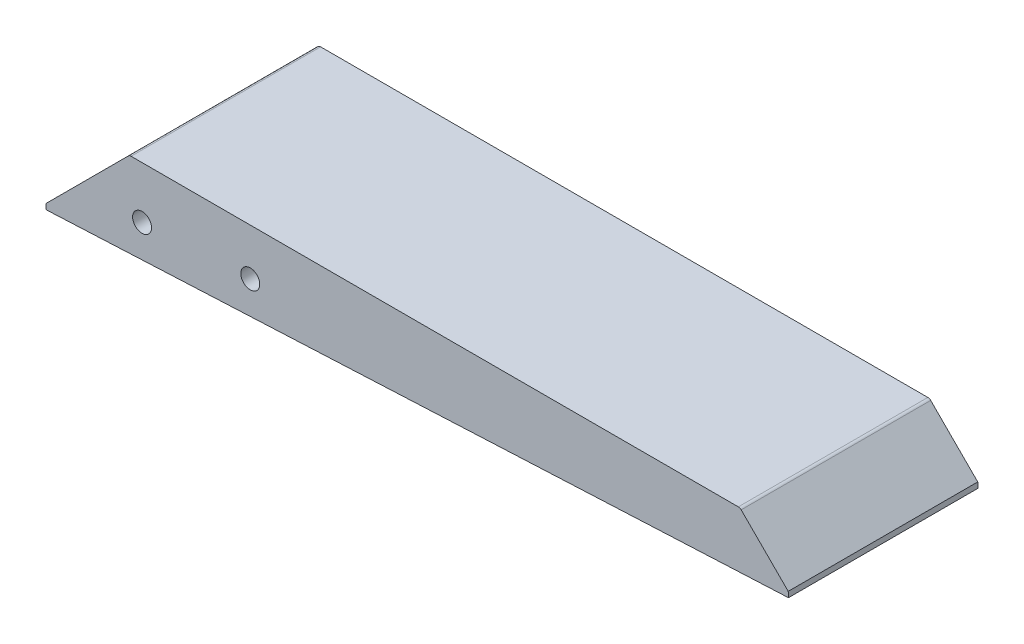
SolidWorks part; units mm, degrees
ref_plane "前视基准面" through (0, 0, 0) normal (0, 0, 1) x (1, 0, 0)
ref_plane "上视基准面" through (0, 0, 0) normal (0, 1, 0) x (1, 0, 0)
ref_plane "右视基准面" through (0, 0, 0) normal (1, 0, 0) x (0, 0, -1)
other "Configuration Table"
sketch "草图1" plane through (0, 0, 0) normal (0, 0, 1) x (1, 0, 0)
  line L0 (166.8324, 7.5944) -> (168.9537, 9.7157) construction
  line L1 (168.9537, 9.7157) -> (160.2639, 18.4056) construction
  line L2 (158.1425, 16.2843) -> (166.8324, 7.5944) construction
  line L3 (157.6217, 19.5) -> (45.4745, 19.5) construction
  line L4 (45.4745, 16.5) -> (157.6217, 16.5) construction
  line L5 (29.7639, 1.0944) -> (44.9537, 16.2843) construction
  line L6 (42.8324, 18.4056) -> (27.6425, 3.2157) construction
  line L7 (27.6425, 3.2157) -> (29.7639, 1.0944) construction
  line L8 (166.8324, 7.5944) -> (168.9537, 9.7157)
  line L9 (168.9537, 9.7157) -> (160.2639, 18.4056)
  line L10 (158.1425, 16.2843) -> (166.8324, 7.5944)
  line L11 (157.6217, 19.5) -> (45.4745, 19.5)
  line L12 (45.4745, 16.5) -> (157.6217, 16.5)
  line L13 (29.7639, 1.0944) -> (44.9537, 16.2843)
  line L14 (42.8324, 18.4056) -> (27.6425, 3.2157)
  line L15 (27.6425, 3.2157) -> (29.7639, 1.0944)
  line L16 (29.7639, 1.0944) -> (166.8324, 7.5944)
  arc A0 (158.1425, 16.2843) -> (157.6217, 16.5) centre (157.6217, 15.7634) ccw construction
  arc A1 (160.2639, 18.4056) -> (157.6217, 19.5) centre (157.6217, 15.7634) ccw construction
  arc A2 (45.4745, 16.5) -> (44.9537, 16.2843) centre (45.4745, 15.7634) ccw construction
  arc A3 (45.4745, 19.5) -> (42.8324, 18.4056) centre (45.4745, 15.7634) ccw construction
  arc A4 (158.1425, 16.2843) -> (157.6217, 16.5) centre (157.6217, 15.7634) ccw
  arc A5 (160.2639, 18.4056) -> (157.6217, 19.5) centre (157.6217, 15.7634) ccw
  arc A6 (45.4745, 16.5) -> (44.9537, 16.2843) centre (45.4745, 15.7634) ccw
  arc A7 (45.4745, 19.5) -> (42.8324, 18.4056) centre (45.4745, 15.7634) ccw
extrude "凸台-拉伸1" add sketch "草图1" against normal blind 35 contours L12 A6 L13 L16 L10 A4 region at (94.8139, 10.1061, 0)
sketch "草图2" plane through (0.015, -0.3163, 0) normal (0.0474, -0.9989, 0) x (0.9989, 0.0474, 0)
  line L0 (165.5048, -1.5) -> (31.2823, -1.5)
  line L1 (31.2823, -1.5) -> (31.2823, -33.5)
  line L2 (31.2823, -33.5) -> (165.5048, -33.5)
  line L3 (165.5048, -33.5) -> (165.5048, -1.5)
  line L4 (167.0048, 0) -> (29.7823, 0)
  line L5 (29.7823, 0) -> (29.7823, -35)
  line L6 (29.7823, -35) -> (167.0048, -35)
  line L7 (167.0048, -35) -> (167.0048, 0)
  line L8 (167.0048, 0) -> (29.7823, 0)
  line L9 (29.7823, 0) -> (29.7823, -35)
  line L10 (29.7823, -35) -> (167.0048, -35)
  line L11 (167.0048, -35) -> (167.0048, 0)
  dimension "D1" = 0
  dimension "D2" = 1.5
extrude "凸台-拉伸2" add sketch "草图2" along normal blind 1
fillet "圆角1" radius 2 4 edges at (31.2859, 0.666, -33.5) (165.3577, 7.0239, -33.5) (165.3577, 7.0239, -1.5) (31.2859, 0.666, -1.5)
sketch "草图3" plane through (0, 0, 0) normal (0, 0, 1) x (1, 0, 0)
  line L0 (166.8797, 6.5955) -> (29.8112, 0.0955) construction
  line L1 (29.8112, 0.0955) -> (29.7639, 1.0944) construction
  circle A0 centre (47.5068, 6.9414) radius 1.75
  circle A1 centre (67.4842, 7.8923) radius 1.75
  dimension "D1" = 3.5
  dimension "D3" = 20
  dimension "D4" = 6
  dimension "D5" = 18
  dimension "D2" = 2
extrude "切除-拉伸1" cut sketch "草图3" against normal blind 6.2
sketch "草图4" plane through (0, 0, -35) normal (0, 0, -1) x (-1, 0, 0)
  circle A0 centre (-47.5068, 6.9414) radius 1.75 construction
  circle A1 centre (-67.4842, 7.8923) radius 1.75 construction
  circle A2 centre (-47.5068, 6.9414) radius 1.75
  circle A3 centre (-67.4842, 7.8923) radius 1.75
extrude "切除-拉伸2" cut sketch "草图4" against normal blind 6.55
sketch "草图6" plane through (0.015, -0.3163, 0) normal (0.0474, -0.9989, 0) x (0.9989, 0.0474, 0)
  line L1199 (144.5332, -18.3417) -> (144.2984, -18.2008)
  line L1200 (144.2984, -18.2008) -> (143.9227, -18.2947)
  line L1201 (143.9227, -18.2947) -> (142.7956, -19.4688)
  line L1202 (142.7956, -19.4688) -> (142.279, -19.8915)
  line L1203 (142.279, -19.8915) -> (142.1381, -19.8915)
  line L1204 (142.1381, -19.8915) -> (142.0911, -19.7506)
  line L1205 (142.0911, -19.7506) -> (142.6547, -18.2478)
  line L1206 (142.6547, -18.2478) -> (142.7016, -17.8251)
  line L1207 (142.7016, -17.8251) -> (142.4668, -17.4963)
  line L1208 (142.4668, -17.4963) -> (141.9972, -17.4494)
  line L1209 (141.9972, -17.4494) -> (141.6684, -17.7312)
  line L1210 (141.6684, -17.7312) -> (141.2457, -18.3887)
  line L1211 (141.2457, -18.3887) -> (140.2595, -19.3749)
  line L1212 (140.2595, -19.3749) -> (139.2263, -20.1263)
  line L1213 (139.2263, -20.1263) -> (138.8036, -20.3142)
  line L1214 (138.8036, -20.3142) -> (138.6157, -20.3142)
  line L1215 (138.6157, -20.3142) -> (138.5218, -20.2203)
  line L1216 (138.5218, -20.2203) -> (138.5218, -19.9854)
  line L1217 (138.5218, -19.9854) -> (138.6627, -19.6097)
  line L1218 (138.6627, -19.6097) -> (139.4611, -18.4356)
  line L1219 (139.4611, -18.4356) -> (139.4611, -18.1069)
  line L1220 (139.4611, -18.1069) -> (139.2732, -17.872)
  line L1221 (139.2732, -17.872) -> (139.0384, -17.7781)
  line L1222 (139.0384, -17.7781) -> (138.6627, -17.872)
  line L1223 (138.6627, -17.872) -> (138.0052, -18.6235)
  line L1224 (138.0052, -18.6235) -> (137.5825, -19.3279)
  line L1225 (137.5825, -19.3279) -> (137.3477, -20.1263)
  line L1226 (137.3477, -20.1263) -> (137.3477, -20.4081)
  line L1227 (137.3477, -20.4081) -> (137.4886, -20.7838)
  line L1228 (137.4886, -20.7838) -> (137.9113, -21.1595)
  line L1229 (137.9113, -21.1595) -> (138.1931, -21.2535)
  line L1230 (138.1931, -21.2535) -> (138.7566, -21.2535)
  line L1231 (138.7566, -21.2535) -> (139.6959, -20.8778)
  line L1232 (139.6959, -20.8778) -> (140.6352, -20.1733)
  line L1233 (140.6352, -20.1733) -> (140.7761, -20.2203)
  line L1234 (140.7761, -20.2203) -> (140.6352, -20.8308)
  line L1235 (140.6352, -20.8308) -> (140.5413, -20.9247)
  line L1236 (140.5413, -20.9247) -> (138.5218, -21.817)
  line L1237 (138.5218, -21.817) -> (137.9582, -22.1928)
  line L1238 (137.9582, -22.1928) -> (137.6295, -22.5215)
  line L1239 (137.6295, -22.5215) -> (137.4416, -22.8503)
  line L1240 (137.4416, -22.8503) -> (137.4416, -23.2729)
  line L1241 (137.4416, -23.2729) -> (137.6765, -23.6487)
  line L1242 (137.6765, -23.6487) -> (138.0052, -23.8835)
  line L1243 (138.0052, -23.8835) -> (138.3809, -24.0244)
  line L1244 (138.3809, -24.0244) -> (139.1793, -24.0713)
  line L1245 (139.1793, -24.0713) -> (139.8368, -23.8835)
  line L1246 (139.8368, -23.8835) -> (140.4473, -23.5078)
  line L1247 (140.4473, -23.5078) -> (141.0109, -22.8503)
  line L1248 (141.0109, -22.8503) -> (141.4806, -21.817)
  line L1249 (141.4806, -21.817) -> (141.6215, -21.3004)
  line L1250 (141.6215, -21.3004) -> (142.8425, -20.596)
  line L1251 (142.8425, -20.596) -> (143.7348, -19.8445)
  line L1252 (143.7348, -19.8445) -> (144.4863, -18.9522)
  line L1253 (144.4863, -18.9522) -> (144.5802, -18.7644)
  line L1254 (144.5802, -18.7644) -> (144.5332, -18.3417)
  line L1255 (140.2125, -21.9579) -> (140.2125, -22.0988)
  line L1256 (140.2125, -22.0988) -> (140.0247, -22.4745)
  line L1257 (140.0247, -22.4745) -> (139.555, -22.9912)
  line L1258 (139.555, -22.9912) -> (139.0854, -23.226)
  line L1259 (139.0854, -23.226) -> (138.6627, -23.226)
  line L1260 (138.6627, -23.226) -> (138.5218, -23.0851)
  line L1261 (138.5218, -23.0851) -> (138.5688, -22.8503)
  line L1262 (138.5688, -22.8503) -> (138.8036, -22.5685)
  line L1263 (138.8036, -22.5685) -> (140.0716, -21.911)
  line L1264 (140.0716, -21.911) -> (140.2125, -21.9579)
  line L1265 (156.9788, -14.8663) -> (156.744, -14.7254)
  line L1266 (156.744, -14.7254) -> (156.4152, -14.7254)
  line L1267 (156.4152, -14.7254) -> (156.1334, -14.9133)
  line L1268 (156.1334, -14.9133) -> (156.0395, -15.1481)
  line L1269 (156.0395, -15.1481) -> (155.9925, -16.0874)
  line L1270 (155.9925, -16.0874) -> (155.5698, -17.1676)
  line L1271 (155.5698, -17.1676) -> (154.7715, -18.3417)
  line L1272 (154.7715, -18.3417) -> (153.9731, -19.0462)
  line L1273 (153.9731, -19.0462) -> (153.6913, -18.9992)
  line L1274 (153.6913, -18.9992) -> (153.6913, -18.3417)
  line L1275 (153.6913, -18.3417) -> (153.8791, -17.7312)
  line L1276 (153.8791, -17.7312) -> (153.8791, -17.3085)
  line L1277 (153.8791, -17.3085) -> (153.6913, -17.0736)
  line L1278 (153.6913, -17.0736) -> (153.5034, -16.9797)
  line L1279 (153.5034, -16.9797) -> (153.2686, -16.9797)
  line L1280 (153.2686, -16.9797) -> (153.0338, -17.0736)
  line L1281 (153.0338, -17.0736) -> (152.8459, -17.2615)
  line L1282 (152.8459, -17.2615) -> (152.3763, -18.1069)
  line L1283 (152.3763, -18.1069) -> (151.39, -19.1401)
  line L1284 (151.39, -19.1401) -> (151.1082, -19.3279)
  line L1285 (151.1082, -19.3279) -> (150.9204, -19.281)
  line L1286 (150.9204, -19.281) -> (150.9673, -18.9053)
  line L1287 (150.9673, -18.9053) -> (151.2022, -18.2478)
  line L1288 (151.2022, -18.2478) -> (152.0006, -16.7919)
  line L1289 (152.0006, -16.7919) -> (151.9536, -16.3692)
  line L1290 (151.9536, -16.3692) -> (151.5779, -16.1344)
  line L1291 (151.5779, -16.1344) -> (151.2022, -16.2283)
  line L1292 (151.2022, -16.2283) -> (150.9204, -16.5101)
  line L1293 (150.9204, -16.5101) -> (150.122, -17.872)
  line L1294 (150.122, -17.872) -> (149.8872, -18.6235)
  line L1295 (149.8872, -18.6235) -> (149.0418, -19.4219)
  line L1296 (149.0418, -19.4219) -> (148.4782, -19.8445)
  line L1297 (148.4782, -19.8445) -> (148.2434, -19.9385)
  line L1298 (148.2434, -19.9385) -> (147.9616, -19.9385)
  line L1299 (147.9616, -19.9385) -> (147.7268, -19.7976)
  line L1300 (147.7268, -19.7976) -> (147.3511, -19.4219)
  line L1301 (147.3511, -19.4219) -> (147.3511, -19.281)
  line L1302 (147.3511, -19.281) -> (149.1827, -17.5433)
  line L1303 (149.1827, -17.5433) -> (149.2766, -17.3554)
  line L1304 (149.2766, -17.3554) -> (149.2766, -17.1206)
  line L1305 (149.2766, -17.1206) -> (149.0418, -16.8388)
  line L1306 (149.0418, -16.8388) -> (148.6661, -16.7919)
  line L1307 (148.6661, -16.7919) -> (148.3373, -16.9328)
  line L1308 (148.3373, -16.9328) -> (146.6466, -18.4826)
  line L1309 (146.6466, -18.4826) -> (146.5057, -18.4826)
  line L1310 (146.5057, -18.4826) -> (145.6604, -17.5433)
  line L1311 (145.6604, -17.5433) -> (145.1907, -17.4963)
  line L1312 (145.1907, -17.4963) -> (145.0029, -17.5903)
  line L1313 (145.0029, -17.5903) -> (144.815, -17.8251)
  line L1314 (144.815, -17.8251) -> (144.815, -18.1069)
  line L1315 (144.815, -18.1069) -> (145.7543, -19.281)
  line L1316 (145.7543, -19.281) -> (145.7543, -19.3749)
  line L1317 (145.7543, -19.3749) -> (144.1106, -21.2065)
  line L1318 (144.1106, -21.2065) -> (143.9227, -21.5822)
  line L1319 (143.9227, -21.5822) -> (143.9697, -21.864)
  line L1320 (143.9697, -21.864) -> (144.2515, -22.0988)
  line L1321 (144.2515, -22.0988) -> (144.5802, -22.0988)
  line L1322 (144.5802, -22.0988) -> (144.815, -22.0049)
  line L1323 (144.815, -22.0049) -> (146.4588, -20.2203)
  line L1324 (146.4588, -20.2203) -> (146.5997, -20.2203)
  line L1325 (146.5997, -20.2203) -> (147.0693, -20.6429)
  line L1326 (147.0693, -20.6429) -> (147.492, -20.8778)
  line L1327 (147.492, -20.8778) -> (148.2904, -20.9247)
  line L1328 (148.2904, -20.9247) -> (149.0888, -20.549)
  line L1329 (149.0888, -20.549) -> (149.7463, -19.9385)
  line L1330 (149.7463, -19.9385) -> (149.8872, -19.9385)
  line L1331 (149.8872, -19.9385) -> (150.169, -20.2672)
  line L1332 (150.169, -20.2672) -> (150.4038, -20.4081)
  line L1333 (150.4038, -20.4081) -> (150.9204, -20.4551)
  line L1334 (150.9204, -20.4551) -> (151.2491, -20.3611)
  line L1335 (151.2491, -20.3611) -> (151.8127, -20.0324)
  line L1336 (151.8127, -20.0324) -> (152.5172, -19.3749)
  line L1337 (152.5172, -19.3749) -> (152.6581, -19.4219)
  line L1338 (152.6581, -19.4219) -> (152.752, -19.6567)
  line L1339 (152.752, -19.6567) -> (153.0338, -19.9385)
  line L1340 (153.0338, -19.9385) -> (153.4565, -20.1263)
  line L1341 (153.4565, -20.1263) -> (154.067, -20.0794)
  line L1342 (154.067, -20.0794) -> (154.5366, -19.8915)
  line L1343 (154.5366, -19.8915) -> (155.2881, -19.3279)
  line L1344 (155.2881, -19.3279) -> (155.7577, -18.8583)
  line L1345 (155.7577, -18.8583) -> (156.2743, -18.1538)
  line L1346 (156.2743, -18.1538) -> (156.744, -17.3085)
  line L1347 (156.744, -17.3085) -> (157.1197, -16.0404)
  line L1348 (157.1197, -16.0404) -> (157.1197, -15.1951)
  line L1349 (157.1197, -15.1951) -> (156.9788, -14.8663)
  line L1599 (103.178, -10.8157) -> (102.5205, -10.4869)
  line L1600 (102.5205, -10.4869) -> (101.7221, -10.2521)
  line L1601 (101.7221, -10.2521) -> (100.2192, -10.2521)
  line L1602 (100.2192, -10.2521) -> (99.5148, -10.5339)
  line L1603 (99.5148, -10.5339) -> (99.0921, -10.8626)
  line L1604 (99.0921, -10.8626) -> (97.4014, -11.6141)
  line L1605 (97.4014, -11.6141) -> (95.8985, -12.1307)
  line L1606 (95.8985, -12.1307) -> (94.8653, -12.2716)
  line L1607 (94.8653, -12.2716) -> (94.6305, -12.4594)
  line L1608 (94.6305, -12.4594) -> (94.5365, -12.6473)
  line L1609 (94.5365, -12.6473) -> (94.5835, -12.9291)
  line L1610 (94.5835, -12.9291) -> (95.0531, -13.3987)
  line L1611 (95.0531, -13.3987) -> (95.4289, -13.5866)
  line L1612 (95.4289, -13.5866) -> (96.0864, -13.7744)
  line L1613 (96.0864, -13.7744) -> (97.6362, -13.7744)
  line L1614 (97.6362, -13.7744) -> (97.824, -14.1032)
  line L1615 (97.824, -14.1032) -> (97.871, -14.9955)
  line L1616 (97.871, -14.9955) -> (97.7771, -15.3242)
  line L1617 (97.7771, -15.3242) -> (96.556, -15.7939)
  line L1618 (96.556, -15.7939) -> (95.8046, -16.2635)
  line L1619 (95.8046, -16.2635) -> (94.9592, -15.9817)
  line L1620 (94.9592, -15.9817) -> (94.4896, -15.9817)
  line L1621 (94.4896, -15.9817) -> (94.1608, -16.1226)
  line L1622 (94.1608, -16.1226) -> (94.0199, -16.2635)
  line L1623 (94.0199, -16.2635) -> (93.926, -16.5453)
  line L1624 (93.926, -16.5453) -> (94.2078, -17.4846)
  line L1625 (94.2078, -17.4846) -> (94.2548, -18.8935)
  line L1626 (94.2548, -18.8935) -> (94.3956, -19.7389)
  line L1627 (94.3956, -19.7389) -> (94.6305, -20.3964)
  line L1628 (94.6305, -20.3964) -> (94.9123, -20.866)
  line L1629 (94.9123, -20.866) -> (95.4758, -21.4296)
  line L1630 (95.4758, -21.4296) -> (95.9924, -21.6644)
  line L1631 (95.9924, -21.6644) -> (96.603, -21.7114)
  line L1632 (96.603, -21.7114) -> (97.3544, -21.4766)
  line L1633 (97.3544, -21.4766) -> (97.5423, -21.4766)
  line L1634 (97.5423, -21.4766) -> (97.5892, -21.6644)
  line L1635 (97.5892, -21.6644) -> (97.4483, -22.3219)
  line L1636 (97.4483, -22.3219) -> (97.2605, -22.7916)
  line L1637 (97.2605, -22.7916) -> (96.7908, -23.3551)
  line L1638 (96.7908, -23.3551) -> (95.1471, -23.8248)
  line L1639 (95.1471, -23.8248) -> (93.6442, -24.1066)
  line L1640 (93.6442, -24.1066) -> (92.7519, -24.1535)
  line L1641 (92.7519, -24.1535) -> (92.4701, -24.2944)
  line L1642 (92.4701, -24.2944) -> (92.1883, -24.6232)
  line L1643 (92.1883, -24.6232) -> (92.0944, -25.0928)
  line L1644 (92.0944, -25.0928) -> (92.3292, -25.6564)
  line L1645 (92.3292, -25.6564) -> (92.7519, -26.0791)
  line L1646 (92.7519, -26.0791) -> (93.4094, -26.4548)
  line L1647 (93.4094, -26.4548) -> (93.973, -26.6426)
  line L1648 (93.973, -26.6426) -> (95.5228, -26.6426)
  line L1649 (95.5228, -26.6426) -> (96.4621, -26.4078)
  line L1650 (96.4621, -26.4078) -> (100.5949, -24.905)
  line L1651 (100.5949, -24.905) -> (102.9431, -24.2005)
  line L1652 (102.9431, -24.2005) -> (103.3658, -24.2475)
  line L1653 (103.3658, -24.2475) -> (103.9764, -25.2807)
  line L1654 (103.9764, -25.2807) -> (104.446, -25.7034)
  line L1655 (104.446, -25.7034) -> (104.9156, -25.9382)
  line L1656 (104.9156, -25.9382) -> (105.3853, -26.0321)
  line L1657 (105.3853, -26.0321) -> (105.9019, -25.9851)
  line L1658 (105.9019, -25.9851) -> (106.4185, -25.7503)
  line L1659 (106.4185, -25.7503) -> (106.7942, -25.3746)
  line L1660 (106.7942, -25.3746) -> (107.029, -24.7641)
  line L1661 (107.029, -24.7641) -> (107.029, -24.2005)
  line L1662 (107.029, -24.2005) -> (106.8881, -23.6839)
  line L1663 (106.8881, -23.6839) -> (106.5594, -23.1203)
  line L1664 (106.5594, -23.1203) -> (105.8549, -22.3689)
  line L1665 (105.8549, -22.3689) -> (104.9156, -21.7114)
  line L1666 (104.9156, -21.7114) -> (103.8824, -21.2417)
  line L1667 (103.8824, -21.2417) -> (103.178, -21.0539)
  line L1668 (103.178, -21.0539) -> (102.6144, -21.1009)
  line L1669 (102.6144, -21.1009) -> (102.4265, -21.1948)
  line L1670 (102.4265, -21.1948) -> (102.2387, -21.4766)
  line L1671 (102.2387, -21.4766) -> (102.3326, -21.8523)
  line L1672 (102.3326, -21.8523) -> (102.6144, -22.181)
  line L1673 (102.6144, -22.181) -> (102.5205, -22.3689)
  line L1674 (102.5205, -22.3689) -> (101.2524, -22.5567)
  line L1675 (101.2524, -22.5567) -> (100.2662, -22.7916)
  line L1676 (100.2662, -22.7916) -> (99.9374, -22.7446)
  line L1677 (99.9374, -22.7446) -> (99.9374, -22.6037)
  line L1678 (99.9374, -22.6037) -> (100.2662, -21.9462)
  line L1679 (100.2662, -21.9462) -> (100.5949, -20.7721)
  line L1680 (100.5949, -20.7721) -> (100.7358, -20.6782)
  line L1681 (100.7358, -20.6782) -> (101.5342, -20.4903)
  line L1682 (101.5342, -20.4903) -> (102.8492, -20.3494)
  line L1683 (102.8492, -20.3494) -> (103.5067, -20.1146)
  line L1684 (103.5067, -20.1146) -> (103.8355, -19.7859)
  line L1685 (103.8355, -19.7859) -> (103.9764, -19.4571)
  line L1686 (103.9764, -19.4571) -> (104.5399, -18.6587)
  line L1687 (104.5399, -18.6587) -> (105.3383, -17.015)
  line L1688 (105.3383, -17.015) -> (105.3383, -16.3575)
  line L1689 (105.3383, -16.3575) -> (105.2444, -16.0757)
  line L1690 (105.2444, -16.0757) -> (105.0096, -15.7)
  line L1691 (105.0096, -15.7) -> (104.1642, -14.9955)
  line L1692 (104.1642, -14.9955) -> (103.6006, -14.7137)
  line L1693 (103.6006, -14.7137) -> (102.5674, -14.4319)
  line L1694 (102.5674, -14.4319) -> (101.5812, -14.4319)
  line L1695 (101.5812, -14.4319) -> (101.2524, -14.5259)
  line L1696 (101.2524, -14.5259) -> (100.8298, -14.4789)
  line L1697 (100.8298, -14.4789) -> (100.7828, -13.9623)
  line L1698 (100.7828, -13.9623) -> (100.6889, -13.7744)
  line L1699 (100.6889, -13.7744) -> (100.6889, -13.6335)
  line L1700 (100.6889, -13.6335) -> (100.7828, -13.5396)
  line L1701 (100.7828, -13.5396) -> (103.2249, -12.9291)
  line L1702 (103.2249, -12.9291) -> (103.7885, -12.4594)
  line L1703 (103.7885, -12.4594) -> (103.9294, -12.1307)
  line L1704 (103.9294, -12.1307) -> (103.8824, -11.6141)
  line L1705 (103.8824, -11.6141) -> (103.7415, -11.3323)
  line L1706 (103.7415, -11.3323) -> (103.178, -10.8157)
  line L1707 (97.7301, -17.2967) -> (97.7301, -19.3162)
  line L1708 (97.7301, -19.3162) -> (97.4014, -19.551)
  line L1709 (97.4014, -19.551) -> (96.8848, -19.598)
  line L1710 (96.8848, -19.598) -> (96.6969, -19.4571)
  line L1711 (96.6969, -19.4571) -> (96.556, -19.0344)
  line L1712 (96.556, -19.0344) -> (96.509, -17.9073)
  line L1713 (96.509, -17.9073) -> (96.6499, -17.7664)
  line L1714 (96.6499, -17.7664) -> (97.5892, -17.2967)
  line L1715 (97.5892, -17.2967) -> (97.7301, -17.2967)
  line L1716 (101.816, -16.3575) -> (102.0508, -16.5453)
  line L1717 (102.0508, -16.5453) -> (102.0978, -16.6862)
  line L1718 (102.0978, -16.6862) -> (102.0508, -17.0619)
  line L1719 (102.0508, -17.0619) -> (101.863, -17.5785)
  line L1720 (101.863, -17.5785) -> (101.3933, -18.3769)
  line L1721 (101.3933, -18.3769) -> (101.0646, -18.6118)
  line L1722 (101.0646, -18.6118) -> (100.7828, -18.6587)
  line L1723 (100.7828, -18.6587) -> (100.7358, -18.1891)
  line L1724 (100.7358, -18.1891) -> (100.8298, -16.5923)
  line L1725 (100.8298, -16.5923) -> (100.9237, -16.4984)
  line L1726 (100.9237, -16.4984) -> (101.2524, -16.4044)
  line L1727 (101.2524, -16.4044) -> (101.816, -16.3575)
  line L1728 (128.0221, -9.9703) -> (127.5524, -9.9234)
  line L1729 (127.5524, -9.9234) -> (126.9419, -10.2991)
  line L1730 (126.9419, -10.2991) -> (124.7815, -12.4594)
  line L1731 (124.7815, -12.4594) -> (124.6406, -12.4594)
  line L1732 (124.6406, -12.4594) -> (123.2787, -10.8626)
  line L1733 (123.2787, -10.8626) -> (122.9969, -10.7218)
  line L1734 (122.9969, -10.7218) -> (122.7151, -10.7218)
  line L1735 (122.7151, -10.7218) -> (122.3394, -10.9566)
  line L1736 (122.3394, -10.9566) -> (122.2455, -11.3323)
  line L1737 (122.2455, -11.3323) -> (122.3864, -11.661)
  line L1738 (122.3864, -11.661) -> (123.7483, -13.3987)
  line L1739 (123.7483, -13.3987) -> (123.7483, -13.5396)
  line L1740 (123.7483, -13.5396) -> (122.1515, -15.4182)
  line L1741 (122.1515, -15.4182) -> (121.541, -16.3105)
  line L1742 (121.541, -16.3105) -> (121.3062, -16.7801)
  line L1743 (121.3062, -16.7801) -> (121.3062, -17.1559)
  line L1744 (121.3062, -17.1559) -> (121.4471, -17.3907)
  line L1745 (121.4471, -17.3907) -> (121.7289, -17.5316)
  line L1746 (121.7289, -17.5316) -> (122.0106, -17.5316)
  line L1747 (122.0106, -17.5316) -> (122.2455, -17.4376)
  line L1748 (122.2455, -17.4376) -> (122.4803, -17.2028)
  line L1749 (122.4803, -17.2028) -> (123.1378, -16.2166)
  line L1750 (123.1378, -16.2166) -> (124.5937, -14.4789)
  line L1751 (124.5937, -14.4789) -> (124.7346, -14.4789)
  line L1752 (124.7346, -14.4789) -> (125.439, -15.0894)
  line L1753 (125.439, -15.0894) -> (125.9556, -15.4182)
  line L1754 (125.9556, -15.4182) -> (126.4253, -15.4651)
  line L1755 (126.4253, -15.4651) -> (126.754, -15.2773)
  line L1756 (126.754, -15.2773) -> (126.848, -15.0894)
  line L1757 (126.848, -15.0894) -> (126.801, -14.7137)
  line L1758 (126.801, -14.7137) -> (125.5799, -13.5396)
  line L1759 (125.5799, -13.5396) -> (125.5799, -13.4457)
  line L1760 (125.5799, -13.4457) -> (128.069, -10.8626)
  line L1761 (128.069, -10.8626) -> (128.2569, -10.5339)
  line L1762 (128.2569, -10.5339) -> (128.2569, -10.2991)
  line L1763 (128.2569, -10.2991) -> (128.0221, -9.9703)
  line L1764 (132.2489, -9.5476) -> (131.8262, -9.4067)
  line L1765 (131.8262, -9.4067) -> (131.4505, -9.4067)
  line L1766 (131.4505, -9.4067) -> (130.9339, -9.5476)
  line L1767 (130.9339, -9.5476) -> (130.4642, -9.8294)
  line L1768 (130.4642, -9.8294) -> (130.3233, -9.8294)
  line L1769 (130.3233, -9.8294) -> (130.2764, -9.4067)
  line L1770 (130.2764, -9.4067) -> (129.9476, -9.078)
  line L1771 (129.9476, -9.078) -> (129.5719, -9.078)
  line L1772 (129.5719, -9.078) -> (129.384, -9.1719)
  line L1773 (129.384, -9.1719) -> (129.1962, -9.4067)
  line L1774 (129.1962, -9.4067) -> (128.2099, -12.1776)
  line L1775 (128.2099, -12.1776) -> (127.3646, -15.2773)
  line L1776 (127.3646, -15.2773) -> (126.848, -18.0012)
  line L1777 (126.848, -18.0012) -> (126.848, -18.6118)
  line L1778 (126.848, -18.6118) -> (127.0828, -18.9405)
  line L1779 (127.0828, -18.9405) -> (127.5055, -19.0344)
  line L1780 (127.5055, -19.0344) -> (127.7403, -18.9405)
  line L1781 (127.7403, -18.9405) -> (127.9751, -18.6587)
  line L1782 (127.9751, -18.6587) -> (128.2099, -17.1089)
  line L1783 (128.2099, -17.1089) -> (128.7735, -14.7607)
  line L1784 (128.7735, -14.7607) -> (129.6189, -14.7137)
  line L1785 (129.6189, -14.7137) -> (130.5112, -14.2441)
  line L1786 (130.5112, -14.2441) -> (130.8869, -13.9623)
  line L1787 (130.8869, -13.9623) -> (131.6853, -13.1639)
  line L1788 (131.6853, -13.1639) -> (132.3898, -12.1307)
  line L1789 (132.3898, -12.1307) -> (132.7185, -11.2853)
  line L1790 (132.7185, -11.2853) -> (132.8124, -10.5339)
  line L1791 (132.8124, -10.5339) -> (132.6246, -9.9234)
  line L1792 (132.6246, -9.9234) -> (132.2489, -9.5476)
  line L1793 (131.5444, -10.44) -> (131.6383, -10.6748)
  line L1794 (131.6383, -10.6748) -> (131.5914, -11.0035)
  line L1795 (131.5914, -11.0035) -> (131.4505, -11.4262)
  line L1796 (131.4505, -11.4262) -> (130.9808, -12.2246)
  line L1797 (130.9808, -12.2246) -> (130.0885, -13.2109)
  line L1798 (130.0885, -13.2109) -> (129.6658, -13.5396)
  line L1799 (129.6658, -13.5396) -> (129.1962, -13.7275)
  line L1800 (129.1962, -13.7275) -> (129.1492, -13.4926)
  line L1801 (129.1492, -13.4926) -> (129.431, -12.7412)
  line L1802 (129.431, -12.7412) -> (130.0415, -11.661)
  line L1803 (130.0415, -11.661) -> (130.8399, -10.7687)
  line L1804 (130.8399, -10.7687) -> (131.3565, -10.44)
  line L1805 (131.3565, -10.44) -> (131.5444, -10.44)
  line L1806 (46.3512, -7.6691) -> (46.2103, -8.0448)
  line L1807 (46.2103, -8.0448) -> (46.2103, -8.3266)
  line L1808 (46.2103, -8.3266) -> (46.4921, -8.8901)
  line L1809 (46.4921, -8.8901) -> (47.0556, -9.4537)
  line L1810 (47.0556, -9.4537) -> (48.6524, -10.6748)
  line L1811 (48.6524, -10.6748) -> (48.5115, -11.2384)
  line L1812 (48.5115, -11.2384) -> (47.8071, -12.7412)
  line L1813 (47.8071, -12.7412) -> (47.8071, -13.023)
  line L1814 (47.8071, -13.023) -> (47.9949, -13.2109)
  line L1815 (47.9949, -13.2109) -> (48.4176, -13.2109)
  line L1816 (48.4176, -13.2109) -> (49.3569, -12.5534)
  line L1817 (49.3569, -12.5534) -> (50.3431, -12.0368)
  line L1818 (50.3431, -12.0368) -> (50.8128, -11.8959)
  line L1819 (50.8128, -11.8959) -> (51.3764, -11.8959)
  line L1820 (51.3764, -11.8959) -> (51.9399, -11.755)
  line L1821 (51.9399, -11.755) -> (52.5974, -11.3792)
  line L1822 (52.5974, -11.3792) -> (52.9262, -11.0505)
  line L1823 (52.9262, -11.0505) -> (53.161, -10.6748)
  line L1824 (53.161, -10.6748) -> (53.3019, -10.0173)
  line L1825 (53.3019, -10.0173) -> (53.161, -9.4537)
  line L1826 (53.161, -9.4537) -> (52.9731, -9.125)
  line L1827 (52.9731, -9.125) -> (52.4565, -8.5614)
  line L1828 (52.4565, -8.5614) -> (52.0808, -8.2796)
  line L1829 (52.0808, -8.2796) -> (50.9537, -7.6691)
  line L1830 (50.9537, -7.6691) -> (49.8735, -7.2934)
  line L1831 (49.8735, -7.2934) -> (48.6524, -7.0585)
  line L1832 (48.6524, -7.0585) -> (47.1965, -7.1055)
  line L1833 (47.1965, -7.1055) -> (46.7269, -7.2934)
  line L1834 (46.7269, -7.2934) -> (46.3512, -7.6691)
  line L1835 (154.2281, -7.4342) -> (154.0403, -7.1994)
  line L1836 (154.0403, -7.1994) -> (153.6646, -7.1994)
  line L1837 (153.6646, -7.1994) -> (152.0678, -8.2796)
  line L1838 (152.0678, -8.2796) -> (151.5042, -8.5144)
  line L1839 (151.5042, -8.5144) -> (151.1755, -8.5614)
  line L1840 (151.1755, -8.5614) -> (151.0815, -8.4675)
  line L1841 (151.0815, -8.4675) -> (151.0815, -8.3266)
  line L1842 (151.0815, -8.3266) -> (151.5042, -7.0116)
  line L1843 (151.5042, -7.0116) -> (151.4573, -6.495)
  line L1844 (151.4573, -6.495) -> (151.2224, -6.2132)
  line L1845 (151.2224, -6.2132) -> (150.9876, -6.1193)
  line L1846 (150.9876, -6.1193) -> (150.518, -6.1662)
  line L1847 (150.518, -6.1662) -> (150.0014, -6.448)
  line L1848 (150.0014, -6.448) -> (149.2969, -7.0585)
  line L1849 (149.2969, -7.0585) -> (149.156, -7.0116)
  line L1850 (149.156, -7.0116) -> (149.109, -6.6359)
  line L1851 (149.109, -6.6359) -> (148.9212, -6.448)
  line L1852 (148.9212, -6.448) -> (148.4515, -6.401)
  line L1853 (148.4515, -6.401) -> (148.2167, -6.5419)
  line L1854 (148.2167, -6.5419) -> (148.0289, -6.8237)
  line L1855 (148.0289, -6.8237) -> (147.5123, -8.0448)
  line L1856 (147.5123, -8.0448) -> (146.7139, -8.8901)
  line L1857 (146.7139, -8.8901) -> (145.9624, -9.5476)
  line L1858 (145.9624, -9.5476) -> (145.8685, -9.5476)
  line L1859 (145.8685, -9.5476) -> (145.8215, -9.3128)
  line L1860 (145.8215, -9.3128) -> (146.573, -7.3873)
  line L1861 (146.573, -7.3873) -> (146.573, -7.1525)
  line L1862 (146.573, -7.1525) -> (146.3851, -6.8707)
  line L1863 (146.3851, -6.8707) -> (146.1973, -6.7767)
  line L1864 (146.1973, -6.7767) -> (145.9155, -6.7767)
  line L1865 (145.9155, -6.7767) -> (145.7276, -6.8707)
  line L1866 (145.7276, -6.8707) -> (145.4928, -7.1525)
  line L1867 (145.4928, -7.1525) -> (144.7883, -8.7492)
  line L1868 (144.7883, -8.7492) -> (144.6005, -9.5007)
  line L1869 (144.6005, -9.5007) -> (144.6005, -10.2051)
  line L1870 (144.6005, -10.2051) -> (144.9292, -10.6748)
  line L1871 (144.9292, -10.6748) -> (145.258, -10.8157)
  line L1872 (145.258, -10.8157) -> (145.5398, -10.8157)
  line L1873 (145.5398, -10.8157) -> (146.0564, -10.6278)
  line L1874 (146.0564, -10.6278) -> (147.0896, -9.7825)
  line L1875 (147.0896, -9.7825) -> (147.2305, -9.7825)
  line L1876 (147.2305, -9.7825) -> (147.3244, -9.9703)
  line L1877 (147.3244, -9.9703) -> (147.5123, -10.1112)
  line L1878 (147.5123, -10.1112) -> (147.9819, -10.1112)
  line L1879 (147.9819, -10.1112) -> (148.3576, -9.7825)
  line L1880 (148.3576, -9.7825) -> (148.7333, -9.2189)
  line L1881 (148.7333, -9.2189) -> (149.8135, -7.9509)
  line L1882 (149.8135, -7.9509) -> (149.9544, -7.9978)
  line L1883 (149.9544, -7.9978) -> (149.9074, -8.7962)
  line L1884 (149.9074, -8.7962) -> (150.0014, -9.078)
  line L1885 (150.0014, -9.078) -> (150.2362, -9.3598)
  line L1886 (150.2362, -9.3598) -> (150.7998, -9.5946)
  line L1887 (150.7998, -9.5946) -> (151.6451, -9.5007)
  line L1888 (151.6451, -9.5007) -> (152.6314, -9.078)
  line L1889 (152.6314, -9.078) -> (153.5237, -8.5144)
  line L1890 (153.5237, -8.5144) -> (153.9464, -8.1387)
  line L1891 (153.9464, -8.1387) -> (154.2281, -7.763)
  line L1892 (154.2281, -7.763) -> (154.2281, -7.4342)
  line L1893 (132.8594, -12.8821) -> (133.0003, -13.2109)
  line L1894 (133.0003, -13.2109) -> (133.2351, -13.4457)
  line L1895 (133.2351, -13.4457) -> (133.5639, -13.5866)
  line L1896 (133.5639, -13.5866) -> (133.8926, -13.5866)
  line L1897 (133.8926, -13.5866) -> (134.644, -13.2109)
  line L1898 (134.644, -13.2109) -> (135.5364, -12.3185)
  line L1899 (135.5364, -12.3185) -> (135.6303, -12.3185)
  line L1900 (135.6303, -12.3185) -> (135.7712, -12.5064)
  line L1901 (135.7712, -12.5064) -> (136.006, -12.6473)
  line L1902 (136.006, -12.6473) -> (136.5226, -12.6473)
  line L1903 (136.5226, -12.6473) -> (136.7574, -12.5534)
  line L1904 (136.7574, -12.5534) -> (137.0862, -12.3185)
  line L1905 (137.0862, -12.3185) -> (137.9315, -11.4262)
  line L1906 (137.9315, -11.4262) -> (138.0255, -11.4262)
  line L1907 (138.0255, -11.4262) -> (138.1664, -11.708)
  line L1908 (138.1664, -11.708) -> (138.4012, -11.8959)
  line L1909 (138.4012, -11.8959) -> (139.0117, -11.9428)
  line L1910 (139.0117, -11.9428) -> (139.6223, -11.5671)
  line L1911 (139.6223, -11.5671) -> (140.0449, -11.1444)
  line L1912 (140.0449, -11.1444) -> (140.7964, -10.2051)
  line L1913 (140.7964, -10.2051) -> (141.3599, -9.3598)
  line L1914 (141.3599, -9.3598) -> (142.0174, -9.6885)
  line L1915 (142.0174, -9.6885) -> (143.0976, -9.8294)
  line L1916 (143.0976, -9.8294) -> (143.1915, -10.0173)
  line L1917 (143.1915, -10.0173) -> (142.7689, -10.393)
  line L1918 (142.7689, -10.393) -> (142.0174, -10.6748)
  line L1919 (142.0174, -10.6748) -> (141.7356, -10.6748)
  line L1920 (141.7356, -10.6748) -> (141.4069, -10.393)
  line L1921 (141.4069, -10.393) -> (141.1721, -10.393)
  line L1922 (141.1721, -10.393) -> (140.9842, -10.4869)
  line L1923 (140.9842, -10.4869) -> (140.7964, -10.6748)
  line L1924 (140.7964, -10.6748) -> (140.7024, -10.9096)
  line L1925 (140.7024, -10.9096) -> (140.7024, -11.1444)
  line L1926 (140.7024, -11.1444) -> (140.7964, -11.3323)
  line L1927 (140.7964, -11.3323) -> (140.9842, -11.5201)
  line L1928 (140.9842, -11.5201) -> (141.5478, -11.708)
  line L1929 (141.5478, -11.708) -> (142.2992, -11.661)
  line L1930 (142.2992, -11.661) -> (143.1915, -11.3323)
  line L1931 (143.1915, -11.3323) -> (143.7081, -11.0035)
  line L1932 (143.7081, -11.0035) -> (144.1778, -10.5339)
  line L1933 (144.1778, -10.5339) -> (144.4126, -10.0642)
  line L1934 (144.4126, -10.0642) -> (144.4126, -9.7355)
  line L1935 (144.4126, -9.7355) -> (144.2248, -9.3128)
  line L1936 (144.2248, -9.3128) -> (143.943, -9.078)
  line L1937 (143.943, -9.078) -> (143.2855, -8.8432)
  line L1938 (143.2855, -8.8432) -> (142.534, -8.7492)
  line L1939 (142.534, -8.7492) -> (142.4871, -8.4675)
  line L1940 (142.4871, -8.4675) -> (143.0506, -7.9509)
  line L1941 (143.0506, -7.9509) -> (143.1915, -7.9978)
  line L1942 (143.1915, -7.9978) -> (143.2385, -8.2326)
  line L1943 (143.2385, -8.2326) -> (143.4264, -8.3735)
  line L1944 (143.4264, -8.3735) -> (143.849, -8.3266)
  line L1945 (143.849, -8.3266) -> (144.1308, -8.0918)
  line L1946 (144.1308, -8.0918) -> (144.4126, -7.6691)
  line L1947 (144.4126, -7.6691) -> (144.4596, -7.2934)
  line L1948 (144.4596, -7.2934) -> (144.3656, -7.0585)
  line L1949 (144.3656, -7.0585) -> (144.2248, -6.9176)
  line L1950 (144.2248, -6.9176) -> (143.896, -6.7767)
  line L1951 (143.896, -6.7767) -> (143.4264, -6.7767)
  line L1952 (143.4264, -6.7767) -> (142.8158, -6.9646)
  line L1953 (142.8158, -6.9646) -> (142.1583, -7.3403)
  line L1954 (142.1583, -7.3403) -> (141.4069, -8.0918)
  line L1955 (141.4069, -8.0918) -> (140.8903, -8.4675)
  line L1956 (140.8903, -8.4675) -> (139.2465, -10.5339)
  line L1957 (139.2465, -10.5339) -> (139.1056, -10.4869)
  line L1958 (139.1056, -10.4869) -> (139.1056, -10.346)
  line L1959 (139.1056, -10.346) -> (139.4344, -9.2189)
  line L1960 (139.4344, -9.2189) -> (139.4344, -8.7023)
  line L1961 (139.4344, -8.7023) -> (139.1526, -8.4205)
  line L1962 (139.1526, -8.4205) -> (138.683, -8.4675)
  line L1963 (138.683, -8.4675) -> (138.4481, -8.7023)
  line L1964 (138.4481, -8.7023) -> (138.0724, -9.5946)
  line L1965 (138.0724, -9.5946) -> (137.7437, -10.1112)
  line L1966 (137.7437, -10.1112) -> (136.8044, -11.2384)
  line L1967 (136.8044, -11.2384) -> (136.6635, -11.1914)
  line L1968 (136.6635, -11.1914) -> (136.6635, -11.0505)
  line L1969 (136.6635, -11.0505) -> (137.0392, -10.0642)
  line L1970 (137.0392, -10.0642) -> (137.274, -9.6416)
  line L1971 (137.274, -9.6416) -> (137.321, -9.125)
  line L1972 (137.321, -9.125) -> (137.0862, -8.8432)
  line L1973 (137.0862, -8.8432) -> (136.9453, -8.7962)
  line L1974 (136.9453, -8.7962) -> (136.5226, -8.8901)
  line L1975 (136.5226, -8.8901) -> (136.1469, -9.4067)
  line L1976 (136.1469, -9.4067) -> (135.7712, -10.1582)
  line L1977 (135.7712, -10.1582) -> (135.5364, -10.8626)
  line L1978 (135.5364, -10.8626) -> (135.0198, -11.4732)
  line L1979 (135.0198, -11.4732) -> (134.1274, -12.3655)
  line L1980 (134.1274, -12.3655) -> (134.0335, -12.3655)
  line L1981 (134.0335, -12.3655) -> (133.9865, -12.0837)
  line L1982 (133.9865, -12.0837) -> (134.0805, -11.5201)
  line L1983 (134.0805, -11.5201) -> (134.4092, -10.2991)
  line L1984 (134.4092, -10.2991) -> (135.4424, -7.81)
  line L1985 (135.4424, -7.81) -> (136.006, -6.0253)
  line L1986 (136.006, -6.0253) -> (136.006, -5.6966)
  line L1987 (136.006, -5.6966) -> (135.7712, -5.3678)
  line L1988 (135.7712, -5.3678) -> (135.2076, -5.3678)
  line L1989 (135.2076, -5.3678) -> (134.9258, -5.6496)
  line L1990 (134.9258, -5.6496) -> (134.5031, -6.401)
  line L1991 (134.5031, -6.401) -> (134.1274, -7.2464)
  line L1992 (134.1274, -7.2464) -> (133.4699, -9.125)
  line L1993 (133.4699, -9.125) -> (133.0473, -10.7218)
  line L1994 (133.0473, -10.7218) -> (132.8594, -11.755)
  line L1995 (132.8594, -11.755) -> (132.8594, -12.8821)
  line L1996 (146.9956, -4.8982) -> (146.573, -4.8982)
  line L1997 (146.573, -4.8982) -> (146.1033, -5.3209)
  line L1998 (146.1033, -5.3209) -> (145.8215, -5.9314)
  line L1999 (145.8215, -5.9314) -> (145.8685, -6.2601)
  line L2000 (145.8685, -6.2601) -> (146.0564, -6.495)
  line L2001 (146.0564, -6.495) -> (146.4321, -6.5889)
  line L2002 (146.4321, -6.5889) -> (146.7608, -6.448)
  line L2003 (146.7608, -6.448) -> (147.1365, -5.9314)
  line L2004 (147.1365, -5.9314) -> (147.3244, -5.3678)
  line L2005 (147.3244, -5.3678) -> (147.2305, -5.086)
  line L2006 (147.2305, -5.086) -> (146.9956, -4.8982)
  line L2007 (83.1712, -24.2944) -> (82.9833, -24.0126)
  line L2008 (82.9833, -24.0126) -> (82.7955, -23.9187)
  line L2009 (82.7955, -23.9187) -> (82.4198, -23.9187)
  line L2010 (82.4198, -23.9187) -> (76.0796, -25.1868)
  line L2011 (76.0796, -25.1868) -> (73.6844, -25.5625)
  line L2012 (73.6844, -25.5625) -> (71.1483, -25.8442)
  line L2013 (71.1483, -25.8442) -> (69.6455, -25.9382)
  line L2014 (69.6455, -25.9382) -> (67.1094, -25.9382)
  line L2015 (67.1094, -25.9382) -> (65.1839, -25.7973)
  line L2016 (65.1839, -25.7973) -> (64.7142, -25.7034)
  line L2017 (64.7142, -25.7034) -> (64.7612, -25.5625)
  line L2018 (64.7612, -25.5625) -> (65.2778, -25.5625)
  line L2019 (65.2778, -25.5625) -> (66.264, -25.1868)
  line L2020 (66.264, -25.1868) -> (67.2033, -24.3414)
  line L2021 (67.2033, -24.3414) -> (67.579, -23.8248)
  line L2022 (67.579, -23.8248) -> (68.0956, -22.7916)
  line L2023 (68.0956, -22.7916) -> (68.3774, -22.0401)
  line L2024 (68.3774, -22.0401) -> (68.7062, -20.7721)
  line L2025 (68.7062, -20.7721) -> (68.941, -19.3162)
  line L2026 (68.941, -19.3162) -> (69.1758, -19.3162)
  line L2027 (69.1758, -19.3162) -> (70.209, -19.7389)
  line L2028 (70.209, -19.7389) -> (71.7119, -20.4903)
  line L2029 (71.7119, -20.4903) -> (74.5767, -22.1341)
  line L2030 (74.5767, -22.1341) -> (75.9856, -22.6037)
  line L2031 (75.9856, -22.6037) -> (76.9719, -22.6037)
  line L2032 (76.9719, -22.6037) -> (77.6764, -22.3219)
  line L2033 (77.6764, -22.3219) -> (78.099, -21.9462)
  line L2034 (78.099, -21.9462) -> (78.3808, -21.3826)
  line L2035 (78.3808, -21.3826) -> (78.3808, -20.7721)
  line L2036 (78.3808, -20.7721) -> (78.2869, -20.4434)
  line L2037 (78.2869, -20.4434) -> (77.8173, -19.7389)
  line L2038 (77.8173, -19.7389) -> (77.3476, -19.3162)
  line L2039 (77.3476, -19.3162) -> (75.9856, -18.5178)
  line L2040 (75.9856, -18.5178) -> (74.3419, -17.9073)
  line L2041 (74.3419, -17.9073) -> (72.6512, -17.4846)
  line L2042 (72.6512, -17.4846) -> (70.5848, -17.1559)
  line L2043 (70.5848, -17.1559) -> (69.1289, -17.0619)
  line L2044 (69.1289, -17.0619) -> (68.894, -16.968)
  line L2045 (68.894, -16.968) -> (68.941, -16.8271)
  line L2046 (68.941, -16.8271) -> (70.8196, -16.1226)
  line L2047 (70.8196, -16.1226) -> (72.1815, -15.4182)
  line L2048 (72.1815, -15.4182) -> (73.3556, -14.6198)
  line L2049 (73.3556, -14.6198) -> (74.201, -13.7744)
  line L2050 (74.201, -13.7744) -> (74.4828, -13.2578)
  line L2051 (74.4828, -13.2578) -> (74.5298, -12.5064)
  line L2052 (74.5298, -12.5064) -> (74.248, -11.8959)
  line L2053 (74.248, -11.8959) -> (73.6844, -11.3792)
  line L2054 (73.6844, -11.3792) -> (73.2148, -11.1444)
  line L2055 (73.2148, -11.1444) -> (72.5573, -10.9566)
  line L2056 (72.5573, -10.9566) -> (71.524, -10.9566)
  line L2057 (71.524, -10.9566) -> (70.6787, -11.2384)
  line L2058 (70.6787, -11.2384) -> (70.3969, -11.6141)
  line L2059 (70.3969, -11.6141) -> (70.4908, -11.9428)
  line L2060 (70.4908, -11.9428) -> (70.6787, -12.1307)
  line L2061 (70.6787, -12.1307) -> (70.6787, -12.3655)
  line L2062 (70.6787, -12.3655) -> (70.5378, -12.6473)
  line L2063 (70.5378, -12.6473) -> (69.5985, -13.8214)
  line L2064 (69.5985, -13.8214) -> (69.0349, -14.385)
  line L2065 (69.0349, -14.385) -> (68.0956, -15.1364)
  line L2066 (68.0956, -15.1364) -> (67.9078, -15.0425)
  line L2067 (67.9078, -15.0425) -> (67.579, -14.5259)
  line L2068 (67.579, -14.5259) -> (66.6398, -13.6335)
  line L2069 (66.6398, -13.6335) -> (66.0762, -13.2578)
  line L2070 (66.0762, -13.2578) -> (65.1369, -12.8351)
  line L2071 (65.1369, -12.8351) -> (65.1369, -12.7412)
  line L2072 (65.1369, -12.7412) -> (66.5928, -11.3792)
  line L2073 (66.5928, -11.3792) -> (67.2503, -10.5809)
  line L2074 (67.2503, -10.5809) -> (67.4381, -10.1582)
  line L2075 (67.4381, -10.1582) -> (67.4381, -9.6416)
  line L2076 (67.4381, -9.6416) -> (67.1564, -9.125)
  line L2077 (67.1564, -9.125) -> (67.2033, -8.9841)
  line L2078 (67.2033, -8.9841) -> (70.5848, -7.763)
  line L2079 (70.5848, -7.763) -> (71.1483, -7.4812)
  line L2080 (71.1483, -7.4812) -> (71.571, -7.0585)
  line L2081 (71.571, -7.0585) -> (71.7589, -6.7298)
  line L2082 (71.7589, -6.7298) -> (71.7589, -5.8375)
  line L2083 (71.7589, -5.8375) -> (71.524, -5.4148)
  line L2084 (71.524, -5.4148) -> (70.9135, -4.8982)
  line L2085 (70.9135, -4.8982) -> (70.256, -4.6164)
  line L2086 (70.256, -4.6164) -> (69.7864, -4.5225)
  line L2087 (69.7864, -4.5225) -> (68.894, -4.5225)
  line L2088 (68.894, -4.5225) -> (68.1896, -4.6634)
  line L2089 (68.1896, -4.6634) -> (67.3912, -4.9451)
  line L2090 (67.3912, -4.9451) -> (62.7417, -7.1525)
  line L2091 (62.7417, -7.1525) -> (60.2526, -8.1857)
  line L2092 (60.2526, -8.1857) -> (57.9983, -8.8901)
  line L2093 (57.9983, -8.8901) -> (56.8712, -9.078)
  line L2094 (56.8712, -9.078) -> (56.3076, -9.078)
  line L2095 (56.3076, -9.078) -> (56.0258, -9.2189)
  line L2096 (56.0258, -9.2189) -> (55.8849, -9.4537)
  line L2097 (55.8849, -9.4537) -> (55.9789, -9.8294)
  line L2098 (55.9789, -9.8294) -> (56.4485, -10.2051)
  line L2099 (56.4485, -10.2051) -> (56.9181, -10.44)
  line L2100 (56.9181, -10.44) -> (57.8105, -10.6748)
  line L2101 (57.8105, -10.6748) -> (58.7498, -10.7687)
  line L2102 (58.7498, -10.7687) -> (59.9239, -10.7218)
  line L2103 (59.9239, -10.7218) -> (61.1919, -10.5339)
  line L2104 (61.1919, -10.5339) -> (61.8494, -10.346)
  line L2105 (61.8494, -10.346) -> (62.0373, -10.346)
  line L2106 (62.0373, -10.346) -> (62.0842, -10.5339)
  line L2107 (62.0842, -10.5339) -> (61.2858, -11.5201)
  line L2108 (61.2858, -11.5201) -> (60.0648, -12.7412)
  line L2109 (60.0648, -12.7412) -> (59.1255, -13.5396)
  line L2110 (59.1255, -13.5396) -> (57.9983, -14.385)
  line L2111 (57.9983, -14.385) -> (56.8712, -15.0894)
  line L2112 (56.8712, -15.0894) -> (56.0258, -15.5121)
  line L2113 (56.0258, -15.5121) -> (55.5092, -15.653)
  line L2114 (55.5092, -15.653) -> (55.3214, -15.7939)
  line L2115 (55.3214, -15.7939) -> (55.2274, -16.0757)
  line L2116 (55.2274, -16.0757) -> (55.4153, -16.3105)
  line L2117 (55.4153, -16.3105) -> (55.744, -16.4514)
  line L2118 (55.744, -16.4514) -> (56.3546, -16.4984)
  line L2119 (56.3546, -16.4984) -> (57.9514, -16.2635)
  line L2120 (57.9514, -16.2635) -> (58.8437, -16.0287)
  line L2121 (58.8437, -16.0287) -> (59.8299, -15.653)
  line L2122 (59.8299, -15.653) -> (60.0648, -15.7)
  line L2123 (60.0648, -15.7) -> (59.9708, -15.9817)
  line L2124 (59.9708, -15.9817) -> (59.6421, -16.3575)
  line L2125 (59.6421, -16.3575) -> (58.1392, -17.6725)
  line L2126 (58.1392, -17.6725) -> (56.4485, -18.8466)
  line L2127 (56.4485, -18.8466) -> (55.838, -19.1753)
  line L2128 (55.838, -19.1753) -> (55.3214, -19.3162)
  line L2129 (55.3214, -19.3162) -> (55.0865, -19.645)
  line L2130 (55.0865, -19.645) -> (55.1805, -19.9268)
  line L2131 (55.1805, -19.9268) -> (55.6501, -20.2555)
  line L2132 (55.6501, -20.2555) -> (56.1667, -20.3964)
  line L2133 (56.1667, -20.3964) -> (57.106, -20.3964)
  line L2134 (57.106, -20.3964) -> (57.5756, -20.3025)
  line L2135 (57.5756, -20.3025) -> (58.5149, -19.9737)
  line L2136 (58.5149, -19.9737) -> (59.3603, -19.551)
  line L2137 (59.3603, -19.551) -> (60.5344, -18.7526)
  line L2138 (60.5344, -18.7526) -> (61.6146, -17.8134)
  line L2139 (61.6146, -17.8134) -> (61.7555, -17.8134)
  line L2140 (61.7555, -17.8134) -> (61.8494, -17.9073)
  line L2141 (61.8494, -17.9073) -> (61.8964, -18.1421)
  line L2142 (61.8964, -18.1421) -> (61.4267, -18.8466)
  line L2143 (61.4267, -18.8466) -> (60.6283, -19.6919)
  line L2144 (60.6283, -19.6919) -> (58.7967, -21.1948)
  line L2145 (58.7967, -21.1948) -> (57.7165, -21.8992)
  line L2146 (57.7165, -21.8992) -> (56.2606, -22.6507)
  line L2147 (56.2606, -22.6507) -> (55.3214, -23.0264)
  line L2148 (55.3214, -23.0264) -> (54.476, -23.2612)
  line L2149 (54.476, -23.2612) -> (54.2881, -23.496)
  line L2150 (54.2881, -23.496) -> (54.3351, -23.6839)
  line L2151 (54.3351, -23.6839) -> (54.6639, -23.9187)
  line L2152 (54.6639, -23.9187) -> (55.1805, -24.0126)
  line L2153 (55.1805, -24.0126) -> (56.4015, -23.9187)
  line L2154 (56.4015, -23.9187) -> (58.2331, -23.543)
  line L2155 (58.2331, -23.543) -> (60.7223, -22.6507)
  line L2156 (60.7223, -22.6507) -> (61.098, -23.4021)
  line L2157 (61.098, -23.4021) -> (62.0842, -24.4823)
  line L2158 (62.0842, -24.4823) -> (62.9765, -25.0928)
  line L2159 (62.9765, -25.0928) -> (63.5871, -25.3746)
  line L2160 (63.5871, -25.3746) -> (64.0098, -25.4685)
  line L2161 (64.0098, -25.4685) -> (64.0098, -25.6564)
  line L2162 (64.0098, -25.6564) -> (54.2881, -24.2944)
  line L2163 (54.2881, -24.2944) -> (51.4703, -24.0596)
  line L2164 (51.4703, -24.0596) -> (51.4233, -23.9187)
  line L2165 (51.4233, -23.9187) -> (51.893, -23.59)
  line L2166 (51.893, -23.59) -> (52.4565, -22.9325)
  line L2167 (52.4565, -22.9325) -> (52.6444, -22.5098)
  line L2168 (52.6444, -22.5098) -> (52.6914, -21.9932)
  line L2169 (52.6914, -21.9932) -> (52.4565, -21.3357)
  line L2170 (52.4565, -21.3357) -> (51.3294, -19.8798)
  line L2171 (51.3294, -19.8798) -> (51.2355, -19.551)
  line L2172 (51.2355, -19.551) -> (51.2355, -19.0814)
  line L2173 (51.2355, -19.0814) -> (51.3294, -18.7526)
  line L2174 (51.3294, -18.7526) -> (51.7051, -18.0951)
  line L2175 (51.7051, -18.0951) -> (53.208, -16.4514)
  line L2176 (53.208, -16.4514) -> (53.3958, -16.0287)
  line L2177 (53.3958, -16.0287) -> (53.3958, -15.7)
  line L2178 (53.3958, -15.7) -> (53.3019, -15.3712)
  line L2179 (53.3019, -15.3712) -> (53.114, -15.0894)
  line L2180 (53.114, -15.0894) -> (52.6914, -14.7137)
  line L2181 (52.6914, -14.7137) -> (52.2217, -14.4789)
  line L2182 (52.2217, -14.4789) -> (51.4703, -14.291)
  line L2183 (51.4703, -14.291) -> (50.531, -14.291)
  line L2184 (50.531, -14.291) -> (49.8265, -14.4789)
  line L2185 (49.8265, -14.4789) -> (49.4978, -14.6668)
  line L2186 (49.4978, -14.6668) -> (49.0281, -15.1834)
  line L2187 (49.0281, -15.1834) -> (46.9617, -16.0757)
  line L2188 (46.9617, -16.0757) -> (45.4119, -16.5923)
  line L2189 (45.4119, -16.5923) -> (44.1439, -16.8271)
  line L2190 (44.1439, -16.8271) -> (43.8151, -17.1089)
  line L2191 (43.8151, -17.1089) -> (43.6742, -17.3907)
  line L2192 (43.6742, -17.3907) -> (43.6742, -17.8603)
  line L2193 (43.6742, -17.8603) -> (43.7681, -18.0482)
  line L2194 (43.7681, -18.0482) -> (44.1439, -18.4239)
  line L2195 (44.1439, -18.4239) -> (44.6135, -18.6587)
  line L2196 (44.6135, -18.6587) -> (45.271, -18.8466)
  line L2197 (45.271, -18.8466) -> (46.3981, -18.8466)
  line L2198 (46.3981, -18.8466) -> (46.9148, -18.7526)
  line L2199 (46.9148, -18.7526) -> (48.7464, -18.1421)
  line L2200 (48.7464, -18.1421) -> (48.7933, -18.33)
  line L2201 (48.7933, -18.33) -> (48.5115, -19.1753)
  line L2202 (48.5115, -19.1753) -> (48.5115, -19.7389)
  line L2203 (48.5115, -19.7389) -> (48.7464, -20.3494)
  line L2204 (48.7464, -20.3494) -> (49.4508, -21.2887)
  line L2205 (49.4508, -21.2887) -> (49.5917, -21.6644)
  line L2206 (49.5917, -21.6644) -> (49.4508, -22.181)
  line L2207 (49.4508, -22.181) -> (49.0751, -22.6037)
  line L2208 (49.0751, -22.6037) -> (48.6055, -22.9325)
  line L2209 (48.6055, -22.9325) -> (47.3844, -23.4491)
  line L2210 (47.3844, -23.4491) -> (42.0305, -24.3414)
  line L2211 (42.0305, -24.3414) -> (39.2126, -25.0928)
  line L2212 (39.2126, -25.0928) -> (38.743, -25.3276)
  line L2213 (38.743, -25.3276) -> (38.4142, -25.6564)
  line L2214 (38.4142, -25.6564) -> (38.2733, -26.0321)
  line L2215 (38.2733, -26.0321) -> (38.2733, -26.3139)
  line L2216 (38.2733, -26.3139) -> (38.4612, -26.7835)
  line L2217 (38.4612, -26.7835) -> (38.743, -27.1123)
  line L2218 (38.743, -27.1123) -> (39.2596, -27.488)
  line L2219 (39.2596, -27.488) -> (40.1989, -27.8168)
  line L2220 (40.1989, -27.8168) -> (41.0442, -27.8637)
  line L2221 (41.0442, -27.8637) -> (42.1244, -27.5819)
  line L2222 (42.1244, -27.5819) -> (44.4726, -26.4548)
  line L2223 (44.4726, -26.4548) -> (46.2103, -25.9851)
  line L2224 (46.2103, -25.9851) -> (48.1828, -25.7503)
  line L2225 (48.1828, -25.7503) -> (50.2962, -25.7503)
  line L2226 (50.2962, -25.7503) -> (52.0808, -25.8912)
  line L2227 (52.0808, -25.8912) -> (54.5699, -26.2669)
  line L2228 (54.5699, -26.2669) -> (57.1999, -26.8305)
  line L2229 (57.1999, -26.8305) -> (64.4794, -28.7091)
  line L2230 (64.4794, -28.7091) -> (67.5321, -29.3666)
  line L2231 (67.5321, -29.3666) -> (70.209, -29.7423)
  line L2232 (70.209, -29.7423) -> (72.6981, -29.7892)
  line L2233 (72.6981, -29.7892) -> (74.201, -29.6014)
  line L2234 (74.201, -29.6014) -> (75.1873, -29.3666)
  line L2235 (75.1873, -29.3666) -> (77.0189, -28.7091)
  line L2236 (77.0189, -28.7091) -> (78.193, -28.1455)
  line L2237 (78.193, -28.1455) -> (80.1655, -26.9714)
  line L2238 (80.1655, -26.9714) -> (81.5744, -25.9851)
  line L2239 (81.5744, -25.9851) -> (82.3728, -25.3276)
  line L2240 (82.3728, -25.3276) -> (83.0303, -24.6701)
  line L2241 (83.0303, -24.6701) -> (83.1712, -24.4353)
  line L2242 (83.1712, -24.4353) -> (83.1712, -24.2944)
  line L2243 (64.5733, -19.3162) -> (64.6203, -19.6919)
  line L2244 (64.6203, -19.6919) -> (64.4324, -20.96)
  line L2245 (64.4324, -20.96) -> (64.1037, -22.0401)
  line L2246 (64.1037, -22.0401) -> (63.8219, -22.5567)
  line L2247 (63.8219, -22.5567) -> (63.3992, -22.8855)
  line L2248 (63.3992, -22.8855) -> (62.7417, -22.9325)
  line L2249 (62.7417, -22.9325) -> (62.0373, -22.6976)
  line L2250 (62.0373, -22.6976) -> (61.5206, -22.4159)
  line L2251 (61.5206, -22.4159) -> (61.5206, -22.228)
  line L2252 (61.5206, -22.228) -> (62.0373, -21.9462)
  line L2253 (62.0373, -21.9462) -> (62.8826, -21.3357)
  line L2254 (62.8826, -21.3357) -> (63.681, -20.5843)
  line L2255 (63.681, -20.5843) -> (64.1037, -20.0676)
  line L2256 (64.1037, -20.0676) -> (64.4324, -19.3632)
  line L2257 (64.4324, -19.3632) -> (64.5733, -19.3162)
  line L2258 (61.1449, -15.1834) -> (62.366, -14.5728)
  line L2259 (62.366, -14.5728) -> (62.9296, -14.1971)
  line L2260 (62.9296, -14.1971) -> (63.1174, -14.1971)
  line L2261 (63.1174, -14.1971) -> (63.5401, -14.6668)
  line L2262 (63.5401, -14.6668) -> (64.0098, -15.4651)
  line L2263 (64.0098, -15.4651) -> (64.2915, -16.2166)
  line L2264 (64.2915, -16.2166) -> (64.3855, -16.8271)
  line L2265 (64.3855, -16.8271) -> (64.1976, -16.921)
  line L2266 (64.1976, -16.921) -> (62.366, -17.1559)
  line L2267 (62.366, -17.1559) -> (62.319, -16.968)
  line L2268 (62.319, -16.968) -> (62.5069, -16.5923)
  line L2269 (62.5069, -16.5923) -> (62.5069, -16.2166)
  line L2270 (62.5069, -16.2166) -> (62.413, -15.9817)
  line L2271 (62.413, -15.9817) -> (62.0373, -15.606)
  line L2272 (62.0373, -15.606) -> (61.8024, -15.4651)
  line L2273 (61.8024, -15.4651) -> (61.1919, -15.3242)
  line L2274 (61.1919, -15.3242) -> (61.1449, -15.1834)
  line L2275 (123.2787, -26.0321) -> (123.0908, -25.1868)
  line L2276 (123.0908, -25.1868) -> (122.856, -24.5762)
  line L2277 (122.856, -24.5762) -> (122.4803, -23.8248)
  line L2278 (122.4803, -23.8248) -> (121.6349, -22.4628)
  line L2279 (121.6349, -22.4628) -> (119.6624, -19.8798)
  line L2280 (119.6624, -19.8798) -> (118.6292, -18.7057)
  line L2281 (118.6292, -18.7057) -> (118.0187, -18.236)
  line L2282 (118.0187, -18.236) -> (117.549, -18.283)
  line L2283 (117.549, -18.283) -> (117.3612, -18.5178)
  line L2284 (117.3612, -18.5178) -> (117.3612, -18.8466)
  line L2285 (117.3612, -18.8466) -> (117.9248, -20.3964)
  line L2286 (117.9248, -20.3964) -> (118.2535, -21.6644)
  line L2287 (118.2535, -21.6644) -> (118.4414, -22.7916)
  line L2288 (118.4414, -22.7916) -> (118.4414, -24.1066)
  line L2289 (118.4414, -24.1066) -> (118.3005, -24.5762)
  line L2290 (118.3005, -24.5762) -> (118.0656, -24.858)
  line L2291 (118.0656, -24.858) -> (117.7369, -24.9989)
  line L2292 (117.7369, -24.9989) -> (116.8446, -24.9989)
  line L2293 (116.8446, -24.9989) -> (115.9053, -24.811)
  line L2294 (115.9053, -24.811) -> (114.919, -24.4823)
  line L2295 (114.919, -24.4823) -> (114.1206, -24.1066)
  line L2296 (114.1206, -24.1066) -> (113.3692, -23.6369)
  line L2297 (113.3692, -23.6369) -> (112.7117, -23.1203)
  line L2298 (112.7117, -23.1203) -> (111.7255, -22.0871)
  line L2299 (111.7255, -22.0871) -> (111.068, -21.1009)
  line L2300 (111.068, -21.1009) -> (110.3635, -19.5041)
  line L2301 (110.3635, -19.5041) -> (109.8939, -17.7194)
  line L2302 (109.8939, -17.7194) -> (109.706, -16.0287)
  line L2303 (109.706, -16.0287) -> (109.753, -14.0562)
  line L2304 (109.753, -14.0562) -> (110.0348, -12.0837)
  line L2305 (110.0348, -12.0837) -> (110.2226, -11.3323)
  line L2306 (110.2226, -11.3323) -> (110.7392, -9.9234)
  line L2307 (110.7392, -9.9234) -> (111.6315, -8.1857)
  line L2308 (111.6315, -8.1857) -> (111.6315, -7.1994)
  line L2309 (111.6315, -7.1994) -> (111.2089, -6.401)
  line L2310 (111.2089, -6.401) -> (110.4105, -5.6026)
  line L2311 (110.4105, -5.6026) -> (109.2364, -4.8042)
  line L2312 (109.2364, -4.8042) -> (108.6728, -4.5225)
  line L2313 (108.6728, -4.5225) -> (107.7335, -4.1937)
  line L2314 (107.7335, -4.1937) -> (107.2169, -4.0998)
  line L2315 (107.2169, -4.0998) -> (105.8549, -4.0998)
  line L2316 (105.8549, -4.0998) -> (104.399, -4.2876)
  line L2317 (104.399, -4.2876) -> (102.4265, -4.6634)
  line L2318 (102.4265, -4.6634) -> (97.4953, -5.9314)
  line L2319 (97.4953, -5.9314) -> (95.4289, -6.6359)
  line L2320 (95.4289, -6.6359) -> (93.879, -7.3403)
  line L2321 (93.879, -7.3403) -> (93.2215, -7.763)
  line L2322 (93.2215, -7.763) -> (92.8458, -8.1387)
  line L2323 (92.8458, -8.1387) -> (92.611, -8.5144)
  line L2324 (92.611, -8.5144) -> (92.5171, -8.5144)
  line L2325 (92.5171, -8.5144) -> (92.1414, -8.1857)
  line L2326 (92.1414, -8.1857) -> (91.249, -7.81)
  line L2327 (91.249, -7.81) -> (90.5915, -7.81)
  line L2328 (90.5915, -7.81) -> (90.2158, -7.9509)
  line L2329 (90.2158, -7.9509) -> (89.8871, -8.2326)
  line L2330 (89.8871, -8.2326) -> (89.7462, -8.4675)
  line L2331 (89.7462, -8.4675) -> (89.6523, -8.8901)
  line L2332 (89.6523, -8.8901) -> (89.6523, -9.3128)
  line L2333 (89.6523, -9.3128) -> (89.8401, -10.4869)
  line L2334 (89.8401, -10.4869) -> (89.8401, -13.3987)
  line L2335 (89.8401, -13.3987) -> (89.7462, -14.7607)
  line L2336 (89.7462, -14.7607) -> (89.3705, -17.4376)
  line L2337 (89.3705, -17.4376) -> (88.8069, -19.8328)
  line L2338 (88.8069, -19.8328) -> (87.8676, -22.5567)
  line L2339 (87.8676, -22.5567) -> (87.0692, -24.1066)
  line L2340 (87.0692, -24.1066) -> (86.8814, -24.2944)
  line L2341 (86.8814, -24.2944) -> (86.6935, -24.2005)
  line L2342 (86.6935, -24.2005) -> (86.5996, -23.4491)
  line L2343 (86.5996, -23.4491) -> (86.3178, -23.1673)
  line L2344 (86.3178, -23.1673) -> (85.989, -23.2143)
  line L2345 (85.989, -23.2143) -> (85.5194, -23.7778)
  line L2346 (85.5194, -23.7778) -> (85.2376, -24.3884)
  line L2347 (85.2376, -24.3884) -> (85.0028, -25.1868)
  line L2348 (85.0028, -25.1868) -> (84.9089, -25.8442)
  line L2349 (84.9089, -25.8442) -> (84.9089, -26.6426)
  line L2350 (84.9089, -26.6426) -> (85.1437, -27.3941)
  line L2351 (85.1437, -27.3941) -> (85.7073, -27.9576)
  line L2352 (85.7073, -27.9576) -> (86.083, -28.0985)
  line L2353 (86.083, -28.0985) -> (86.7874, -28.0985)
  line L2354 (86.7874, -28.0985) -> (87.351, -27.9107)
  line L2355 (87.351, -27.9107) -> (88.2433, -27.3471)
  line L2356 (88.2433, -27.3471) -> (89.1356, -26.5017)
  line L2357 (89.1356, -26.5017) -> (89.981, -25.4216)
  line L2358 (89.981, -25.4216) -> (90.9203, -23.8718)
  line L2359 (90.9203, -23.8718) -> (91.6248, -22.3219)
  line L2360 (91.6248, -22.3219) -> (92.3292, -20.3494)
  line L2361 (92.3292, -20.3494) -> (93.1746, -16.7332)
  line L2362 (93.1746, -16.7332) -> (93.4094, -15.0425)
  line L2363 (93.4094, -15.0425) -> (93.5503, -13.2578)
  line L2364 (93.5503, -13.2578) -> (93.5503, -11.0505)
  line L2365 (93.5503, -11.0505) -> (93.3624, -9.9703)
  line L2366 (93.3624, -9.9703) -> (93.4564, -9.7825)
  line L2367 (93.4564, -9.7825) -> (94.7714, -9.7825)
  line L2368 (94.7714, -9.7825) -> (100.5949, -7.8569)
  line L2369 (100.5949, -7.8569) -> (103.5537, -7.1055)
  line L2370 (103.5537, -7.1055) -> (105.4792, -6.7767)
  line L2371 (105.4792, -6.7767) -> (106.3246, -6.8237)
  line L2372 (106.3246, -6.8237) -> (106.5594, -7.0585)
  line L2373 (106.5594, -7.0585) -> (106.6533, -7.2934)
  line L2374 (106.6533, -7.2934) -> (106.6533, -8.2796)
  line L2375 (106.6533, -8.2796) -> (106.2306, -11.5201)
  line L2376 (106.2306, -11.5201) -> (106.0898, -14.4789)
  line L2377 (106.0898, -14.4789) -> (106.1837, -17.0619)
  line L2378 (106.1837, -17.0619) -> (106.5124, -19.1284)
  line L2379 (106.5124, -19.1284) -> (106.9351, -20.5373)
  line L2380 (106.9351, -20.5373) -> (107.6865, -22.275)
  line L2381 (107.6865, -22.275) -> (108.6728, -23.8718)
  line L2382 (108.6728, -23.8718) -> (109.753, -25.1868)
  line L2383 (109.753, -25.1868) -> (111.3967, -26.6426)
  line L2384 (111.3967, -26.6426) -> (112.4299, -27.3471)
  line L2385 (112.4299, -27.3471) -> (113.8858, -28.1455)
  line L2386 (113.8858, -28.1455) -> (115.1539, -28.6621)
  line L2387 (115.1539, -28.6621) -> (116.7976, -29.1318)
  line L2388 (116.7976, -29.1318) -> (117.8778, -29.3196)
  line L2389 (117.8778, -29.3196) -> (119.0049, -29.4135)
  line L2390 (119.0049, -29.4135) -> (119.8033, -29.4135)
  line L2391 (119.8033, -29.4135) -> (120.9305, -29.2726)
  line L2392 (120.9305, -29.2726) -> (121.8228, -28.9909)
  line L2393 (121.8228, -28.9909) -> (122.4803, -28.5682)
  line L2394 (122.4803, -28.5682) -> (122.856, -28.1455)
  line L2395 (122.856, -28.1455) -> (123.1848, -27.441)
  line L2396 (123.1848, -27.441) -> (123.2787, -26.9244)
  line L2397 (123.2787, -26.9244) -> (123.2787, -26.0321)
extrude "凸台-拉伸3" add sketch "草图6" along normal blind 1
